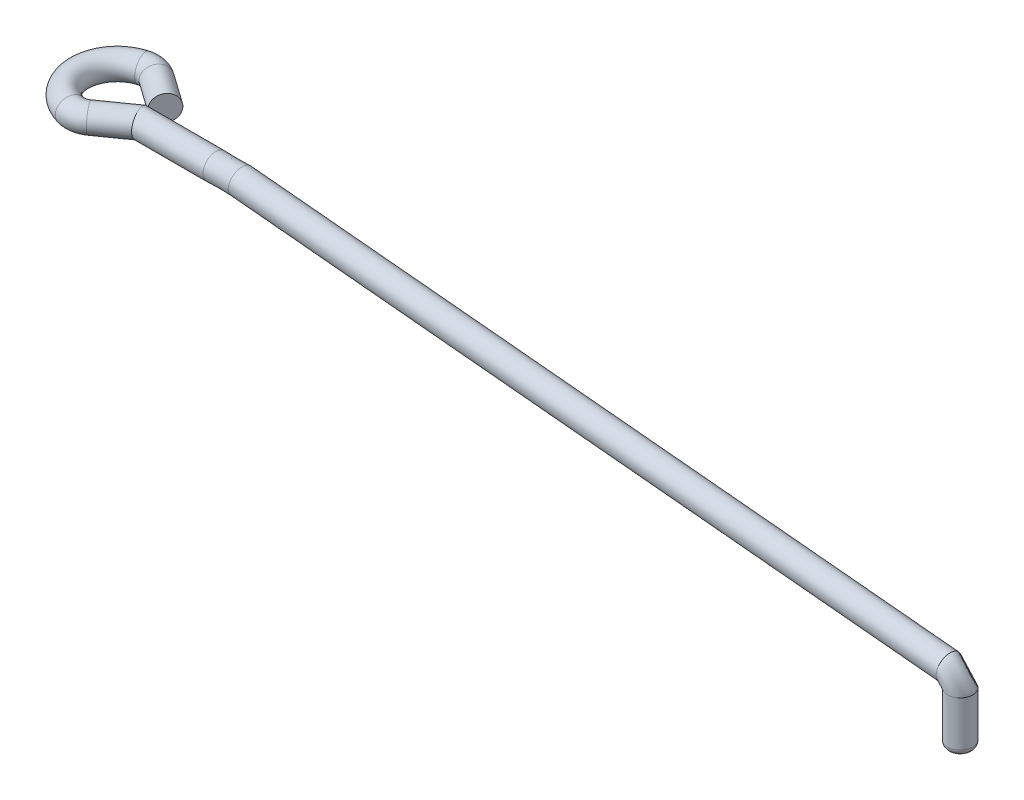
SolidWorks part; units mm, degrees
ref_plane "Front Plane" through (0, 0, 0) normal (0, 0, 1) x (1, 0, 0)
ref_plane "Top Plane" through (0, 0, 0) normal (0, 1, 0) x (1, 0, 0)
ref_plane "Right Plane" through (0, 0, 0) normal (1, 0, 0) x (0, 0, -1)
sketch "Sketch1" plane through (0, 0, 0) normal (0, 0, 1) x (1, 0, 0)
  line L0 (34, -2.5) -> (34, -0.5)
  dimension "D1" = 34
  dimension "D2" = 2
  dimension "D3" = 0.5
sweep "Sweep1" add path "Sketch1" circular profile diameter 1 parameters "D3"=1
ref_plane "Plane1" through (0, 2.7, 0) normal (0, 1, 0) x (1, 0, 0)
sketch "Sketch2" plane through (0, 2.7, 0) normal (0, 1, 0) x (1, 0, 0)
  line L0 (0.233, -0.8352) -> (1.4142, 0)
  line L1 (0.233, 1.8352) -> (1.4142, 1)
  line L2 (1.4142, 0) -> (4.4142, 0)
  line L3 (0, -1) -> (0.233, -0.8352) construction
  line L4 (0, 2) -> (0.233, 1.8352) construction
  line L5 (1.4142, 1) -> (1.4142, 0) construction
  line L6 (0, -1) -> (0, 0) construction
  line L7 (0, 0) -> (1.4142, 0) construction
  arc A0 (1.4142, 0) -> (1.4142, 1) centre (0, 0.5) ccw construction
  arc A1 (-0.4, -0.9457) -> (0.233, -0.8352) centre (-0.2, -0.2228) ccw
  arc A2 (-0.4, 1.9457) -> (0.233, 1.8352) centre (-0.2, 1.2228) cw
  arc A3 (-0.4, 1.9457) -> (-0.4, -0.9457) centre (0, 0.5) ccw
  arc A4 (0, -1) -> (1.4142, 0) centre (0, 0.5) ccw construction
  arc A5 (1.4142, 1) -> (0, 2) centre (0, 0.5) ccw construction
  dimension "D1" = 3
  dimension "D3" = 0.75
  dimension "D2" = 1
  dimension "D4" = 3
sweep "Sweep2" add path "Sketch2" circular profile diameter 1 parameters "D3"=1
sketch "Sketch3" plane through (0, 0, 0) normal (0, 0, 1) x (1, 0, 0)
  line L0 (5.4142, 2.7) -> (33.547, 0.0428)
  line L1 (34, -0.455) -> (34, -0.5)
  line L2 (34.5, -0.5) -> (33.5, -0.5) construction
  line L3 (1.4142, 2.7) -> (4.4142, 2.7) construction
  line L5 (4.4142, 2.2) -> (4.4142, 3.2) construction
  arc A0 (33.547, 0.0428) -> (34, -0.455) centre (33.5, -0.455) cw
  point P18 (34, 0)
  dimension "D2" = 0.5
  dimension "D1" = 0.5
  dimension "D3" = 1
sweep "Sweep3" add path "Sketch3" circular profile diameter 1 parameters "D3"=1
loft "Loft1" add section face at (4.4142, 2.7, 0.5) section face at (5.4142, 2.7, 0.5) connector at (4.4142, 2.2682, 0.2521) connector at (5.3676, 2.206, 0.0613)
fillet "Fillet2" radius 0.25 1 edges at (34, -2.5, 0.5)
ref_plane "Plane2" through (0, 0, -0.5) normal (0, 0, 1) x (1, 0, 0)
